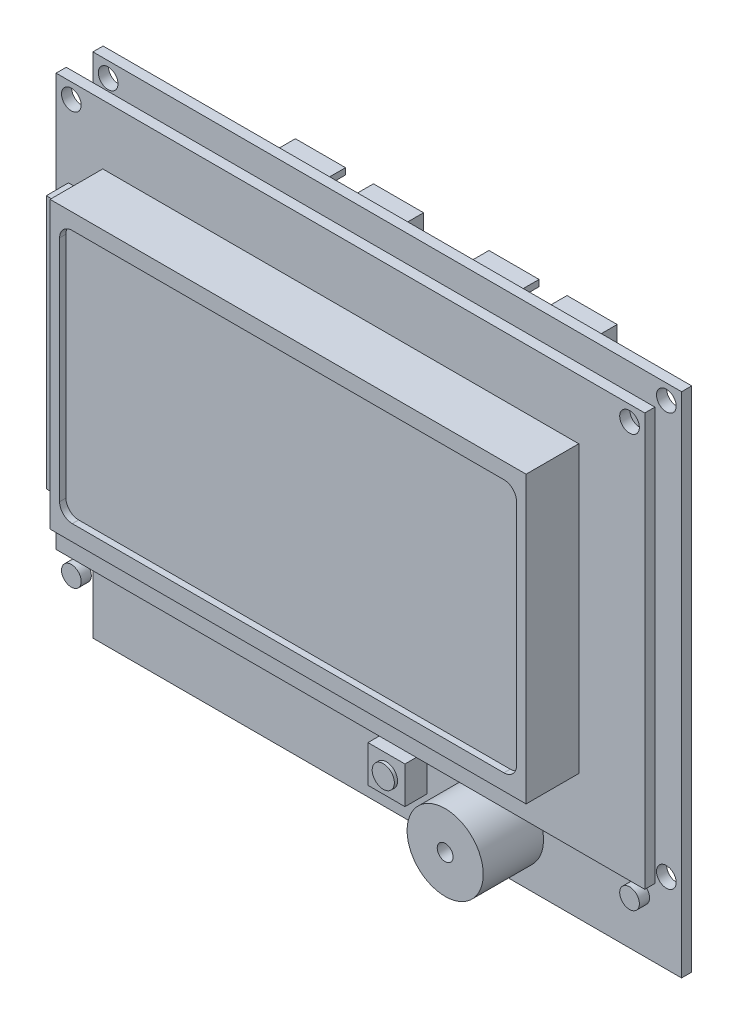
SolidWorks part; units mm, degrees
ref_plane "Front Plane" through (0, 0, 0) normal (0, 0, 1) x (1, 0, 0)
ref_plane "Top Plane" through (0, 0, 0) normal (0, 1, 0) x (1, 0, 0)
ref_plane "Right Plane" through (0, 0, 0) normal (1, 0, 0) x (0, 0, -1)
sketch "Sketch1" plane through (0, 0, 0) normal (0, 0, 1) x (1, 0, 0)
  line L1 (-46.375, -40) -> (46.375, -40)
  line L2 (-46.375, -40) -> (-46.375, 40)
  line L3 (-46.375, 40) -> (46.375, 40)
  line L4 (46.375, -40) -> (46.375, 40)
  line L6 (-43.975, 37.6) -> (43.975, 37.6) construction
  line L7 (-43.975, 37.6) -> (-43.975, -27.4) construction
  line L8 (-43.975, -27.4) -> (43.975, -27.4) construction
  line L9 (43.975, 37.6) -> (43.975, -27.4) construction
  circle A0 centre (-43.975, 37.6) radius 1.55
  circle A1 centre (43.975, 37.6) radius 1.55
  circle A2 centre (43.975, -27.4) radius 1.55
  circle A3 centre (-43.975, -27.4) radius 1.55
  point P5 (0, 40)
  point P6 (-46.375, 0)
  dimension "D3" = 3.1
  dimension "D1" = 80
  dimension "D2" = 92.75
  dimension "D4" = 2.4
  dimension "D5" = 2.4
  dimension "D6" = 2.4
  dimension "D7" = 65
extrude "Boss-Extrude1 - First PCB" add sketch "Sketch1" along normal blind 1.6
sketch "Sketch2" plane through (0, 0, 1.6) normal (0, 0, 1) x (1, 0, 0)
  line L0 (-46.375, -40) -> (46.375, -40) construction
  line L1 (-46.375, -40) -> (-46.375, 40) construction
  circle A0 centre (18.625, -32) radius 6
  dimension "D1" = 12
  dimension "D2" = 8
  dimension "D3" = 65
extrude "Boss-Extrude2 - Speaker" add sketch "Sketch2" along normal blind 9.5
sketch "Sketch15" plane through (0, 0, 11.1) normal (0, 0, 1) x (1, 0, 0)
  circle A0 centre (18.625, -32) radius 1.25
  dimension "D1" = 2.5
extrude "Cut-Extrude1 - Speaker Hole" cut sketch "Sketch15" against normal blind 5
sketch "Sketch3" plane through (0, 0, 1.6) normal (0, 0, 1) x (-1, 0, 0)
  line L1 (-42.375, 37.825) -> (-30.375, 37.825)
  line L2 (-42.375, 37.825) -> (-42.375, 26.175)
  line L3 (-42.375, 26.175) -> (-30.375, 26.175)
  line L4 (-30.375, 37.825) -> (-30.375, 26.175)
  line L8 (-30.375, 32) -> (-18.625, 32) construction
  line L10 (-36.375, 37.825) -> (-36.375, 26.175) construction
  line L11 (-46.375, 40) -> (-46.375, -40) construction
  circle A1 centre (-18.625, 32) radius 6 construction
  point P19 (-12.6367, 31.6254)
  dimension "D1" = 11.65
  dimension "D2" = 12
  dimension "D3" = 10
sketch "Sketch4" plane through (0, 0, 1.6) normal (0, 0, 1) x (-1, 0, 0)
  line L0 (-3.375, 34.915) -> (-3.375, 29.085) construction
  line L1 (-6.29, 34.915) -> (-0.46, 34.915)
  line L2 (-6.29, 34.915) -> (-6.29, 29.085)
  line L3 (-6.29, 29.085) -> (-0.46, 29.085)
  line L4 (-0.46, 34.915) -> (-0.46, 29.085)
  line L5 (-6.29, 32) -> (-0.46, 32) construction
  line L6 (-6.29, 32) -> (-18.625, 32) construction
  line L15 (-46.375, 40) -> (-46.375, -40) construction
  point P8 (-3.375, 32)
  dimension "D1" = 5.83
  dimension "D2" = 5.83
  dimension "D3" = 43
extrude "Boss-Extrude4 - Reset Switch" add sketch "Sketch4" along normal blind 3.5
sketch "Sketch5" plane through (0, 0, 5.1) normal (0, 0, 1) x (-1, 0, 0)
  line L1 (-6.29, 34.915) -> (-0.46, 29.085) construction
  line L2 (-0.46, 34.915) -> (-6.29, 29.085) construction
  circle A0 centre (-3.375, 32) radius 1.75
  dimension "D1" = 3.5
extrude "Boss-Extrude5 - Reset Button" add sketch "Sketch5" along normal blind 0.5
sketch "Sketch19" plane through (0, 0, 1.6) normal (0, 0, 1) x (1, 0, 0)
  line L0 (-46.375, 40) -> (-46.375, -40) construction
  line L1 (-33.375, -19.5) -> (16.625, -19.5)
  line L2 (-33.375, -19.5) -> (-33.375, -22)
  line L3 (-33.375, -22) -> (16.625, -22)
  line L4 (16.625, -19.5) -> (16.625, -22)
  line L5 (-46.375, -40) -> (46.375, -40) construction
  dimension "D1" = 2.5
  dimension "D2" = 50
  dimension "D3" = 13
  dimension "D4" = 18
extrude "Boss-Extrude10 - Connector" add sketch "Sketch19" along normal blind 4.2
sketch "Sketch11" plane through (0, -2, 5.8) normal (0, 0, -1) x (1, 0, 0)
  line L1 (46.375, 23) -> (-46.375, 23)
  line L2 (46.375, 23) -> (46.375, -42)
  line L3 (46.375, -42) -> (-46.375, -42)
  line L4 (-46.375, 23) -> (-46.375, -42)
  line L8 (46.375, 38) -> (46.375, -42) construction
  circle A0 centre (-43.975, -39.6) radius 1.55 construction
  circle A1 centre (-43.975, -39.6) radius 1.55
  circle A2 centre (-43.975, 25.4) radius 1.55 construction
  circle A3 centre (43.975, -39.6) radius 1.55 construction
  circle A4 centre (43.975, 25.4) radius 1.55 construction
  circle A5 centre (-43.975, 25.4) radius 1.55
  circle A6 centre (43.975, -39.6) radius 1.55
  circle A7 centre (43.975, 25.4) radius 1.55
  dimension "D2" = 65
extrude "Boss-Extrude11 - Upper PCB" add sketch "Sketch11" against normal blind 1.6
sketch "Sketch12" plane through (0, 0, 7.4) normal (0, 0, 1) x (-1, 0, 0)
  line L1 (-35.975, 14.4) -> (39.025, 14.4)
  line L2 (-35.975, 14.4) -> (-35.975, -30.6)
  line L3 (-35.975, -30.6) -> (39.025, -30.6)
  line L4 (39.025, 14.4) -> (39.025, -30.6)
  line L6 (46.375, -40) -> (-46.375, -40) construction
  line L7 (46.375, 25) -> (46.375, -40) construction
  dimension "D1" = 45
  dimension "D2" = 75
  dimension "D3" = 9.4
  dimension "D4" = 7.35
extrude "Boss-Extrude12 - LCD" add sketch "Sketch12" along normal blind 8.3
sketch "Sketch24" plane through (0, 0, 7.4) normal (0, 0, 1) x (1, 0, 0)
  line L0 (-39.025, 30.6) -> (-39.025, -14.4) construction
  line L1 (-39.025, 26) -> (-44.425, 26)
  line L2 (-39.025, 26) -> (-39.025, -14)
  line L3 (-39.025, -14) -> (-44.425, -14)
  line L4 (-44.425, 26) -> (-44.425, -14)
  line L5 (35.975, 30.6) -> (-39.025, 30.6) construction
  dimension "D1" = 5.4
  dimension "D2" = 40
  dimension "D3" = 4.6
extrude "Boss-Extrude13 - LCD Bumpout" add sketch "Sketch24" along normal blind 3.5
sketch "Sketch13" plane through (0, 0, 15.7) normal (0, 0, 1) x (-1, 0, 0)
  line L0 (1.525, 14.4) -> (1.525, -30.6) construction
  line L2 (-35.975, -30.6) -> (39.025, -30.6) construction
  line L3 (-35.975, -8.1) -> (39.025, -8.1) construction
  line L4 (-35.975, 14.4) -> (-35.975, -30.6) construction
  line L5 (39.025, -30.6) -> (39.025, 14.4) construction
  line L6 (1.525, 11.9) -> (1.525, -28.1) construction
  line L7 (-32.475, 11.9) -> (35.525, 11.9)
  line L8 (-34.475, 9.9) -> (-34.475, -26.1)
  line L9 (-32.475, -28.1) -> (35.525, -28.1)
  line L10 (37.525, 9.9) -> (37.525, -26.1)
  line L11 (-35.975, 14.4) -> (39.025, 14.4) construction
  arc A8 (35.525, 11.9) -> (37.525, 9.9) centre (35.525, 9.9) cw
  arc A9 (-34.475, -26.1) -> (-32.475, -28.1) centre (-32.475, -26.1) ccw
  arc A10 (-32.475, 11.9) -> (-34.475, 9.9) centre (-32.475, 9.9) ccw
  arc A11 (35.525, -28.1) -> (37.525, -26.1) centre (35.525, -26.1) ccw
  point P18 (1.525, -8.1)
  point P19 (1.525, -8.1)
  point P62 (-34.475, -28.1)
  point P65 (-34.475, 11.9)
  dimension "D8" = 2
  dimension "D1" = 40
  dimension "D2" = 72
extrude "Cut-Extrude2 - Screen Recess" cut sketch "Sketch13" against normal blind 1 contours L10 L7 L8 L9 region at (-1.525, 8.1, 15.7)
sketch "Sketch21" plane through (0, 0, 0) normal (0, 0, -1) x (-1, 0, 0)
  line L0 (-46.375, -40) -> (-46.375, 40) construction
  line L1 (-25.625, 33.5) -> (-5.425, 33.5)
  line L2 (-25.625, 33.5) -> (-25.625, 24.65)
  line L3 (-25.625, 24.65) -> (-5.425, 24.65)
  line L4 (-5.425, 33.5) -> (-5.425, 24.65)
  line L5 (4.875, 33.5) -> (25.075, 33.5)
  line L6 (4.875, 33.5) -> (4.875, 24.65)
  line L7 (4.875, 24.65) -> (25.075, 24.65)
  line L8 (25.075, 33.5) -> (25.075, 24.65)
  line L9 (-46.375, 40) -> (46.375, 40) construction
  line L10 (-24.625, 32.5) -> (-6.425, 32.5)
  line L11 (-6.425, 32.5) -> (-6.425, 25.65)
  line L12 (-24.625, 25.65) -> (-6.425, 25.65)
  line L13 (-24.625, 32.5) -> (-24.625, 25.65)
  line L14 (5.875, 32.5) -> (24.075, 32.5)
  line L15 (24.075, 32.5) -> (24.075, 25.65)
  line L16 (5.875, 25.65) -> (24.075, 25.65)
  line L17 (5.875, 32.5) -> (5.875, 25.65)
  dimension "D1" = 20.2
  dimension "D2" = 10.3
  dimension "D3" = 8.85
  dimension "D4" = 20.75
  dimension "D5" = 6.5
  dimension "D6" = 1
  dimension "D7" = 1
extrude "Boss-Extrude14 - Connectors" add sketch "Sketch21" along normal blind 9
sketch "Sketch22" plane through (0, 0, 0) normal (0, 0, -1) x (-1, 0, 0)
  line L4 (-24.625, 32.5) -> (-24.625, 25.65)
  line L5 (-24.625, 25.65) -> (-6.425, 25.65)
  line L6 (-6.425, 25.65) -> (-6.425, 32.5)
  line L7 (-6.425, 32.5) -> (-24.625, 32.5)
  line L8 (-24.625, 32.5) -> (-24.625, 25.65)
  line L9 (-24.625, 25.65) -> (-6.425, 25.65)
  line L10 (-6.425, 25.65) -> (-6.425, 32.5)
  line L11 (-6.425, 32.5) -> (-24.625, 32.5)
  line L12 (5.875, 32.5) -> (5.875, 25.65)
  line L13 (5.875, 25.65) -> (24.075, 25.65)
  line L14 (24.075, 25.65) -> (24.075, 32.5)
  line L15 (24.075, 32.5) -> (5.875, 32.5)
  line L16 (5.875, 32.5) -> (5.875, 25.65)
  line L17 (5.875, 25.65) -> (24.075, 25.65)
  line L18 (24.075, 25.65) -> (24.075, 32.5)
  line L19 (24.075, 32.5) -> (5.875, 32.5)
  dimension "D1" = 0
  dimension "D2" = 0
extrude "Boss-Extrude15 - Connector Recess" add sketch "Sketch22" along normal blind 2.55
sketch "Sketch23" plane through (0, 0, -9) normal (0, 0, -1) x (-1, 0, 0)
  line L0 (-5.425, 33.5) -> (-25.625, 33.5) construction
  line L1 (-17.725, 33.5) -> (-13.325, 33.5)
  line L2 (-17.725, 33.5) -> (-17.725, 32.5)
  line L3 (-17.725, 32.5) -> (-13.325, 32.5)
  line L4 (-13.325, 33.5) -> (-13.325, 32.5)
  line L5 (-6.425, 32.5) -> (-24.625, 32.5) construction
  line L6 (25.075, 33.5) -> (4.875, 33.5) construction
  line L7 (12.775, 33.5) -> (17.175, 33.5)
  line L8 (12.775, 33.5) -> (12.775, 32.5)
  line L9 (12.775, 32.5) -> (17.175, 32.5)
  line L10 (17.175, 33.5) -> (17.175, 32.5)
  line L11 (24.075, 32.5) -> (5.875, 32.5) construction
  line L12 (14.975, 25.65) -> (14.975, 33.5) construction
  line L13 (5.875, 25.65) -> (24.075, 25.65) construction
  line L14 (-15.525, 25.65) -> (-15.525, 33.5) construction
  line L15 (-24.625, 25.65) -> (-6.425, 25.65) construction
  point P20 (14.975, 33.5)
  point P25 (-15.525, 33.5)
  dimension "D1" = 4.4
extrude "Cut-Extrude3 - Connector Notch" cut sketch "Sketch23" against normal up to surface (6.45 mm away) up to face at (15.525, 29.075, -2.55)
